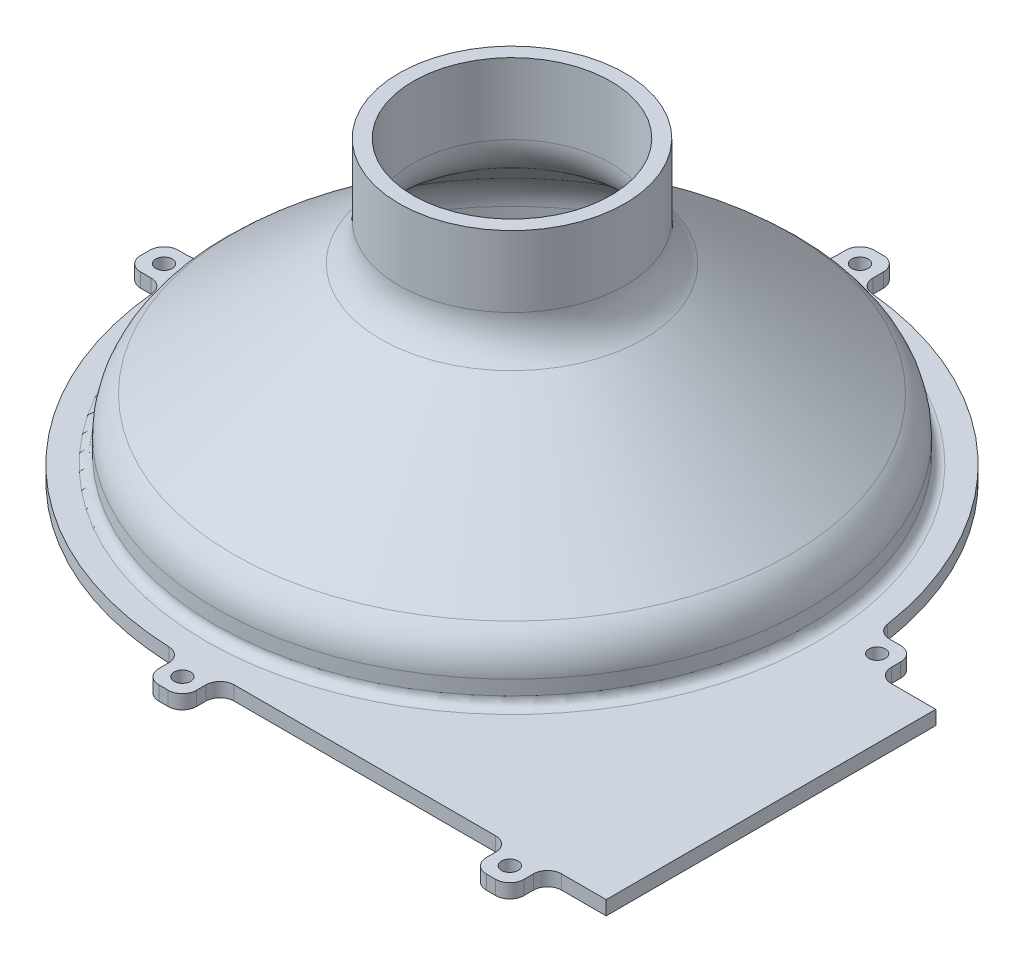
SolidWorks part; units mm, degrees
ref_plane "Front Plane" through (0, 0, 0) normal (0, 0, 1) x (1, 0, 0)
ref_plane "Top Plane" through (0, 0, 0) normal (0, 1, 0) x (1, 0, 0)
ref_plane "Right Plane" through (0, 0, 0) normal (1, 0, 0) x (0, 0, -1)
sketch "Sketch2" plane through (0, 0, 0) normal (0, 1, 0) x (1, 0, 0)
  line L0 (70, 0) -> (70, -70) construction
  line L1 (0, -70) -> (90, -70)
  line L3 (70, 0) -> (90, 0)
  line L4 (90, -70) -> (90, 0)
  arc A0 (70, 0) -> (0, -70) centre (0, 0) ccw
  circle A1 centre (0, 0) radius 60
  dimension "D1" = 140
  dimension "D4" = 120
  dimension "D3" = 20
extrude "Boss-Extrude1" add sketch "Sketch2" along normal blind 3
sketch "Sketch3" plane through (0, 3, 0) normal (0, 1, 0) x (1, 0, 0)
  circle A2 centre (0, 0) radius 60 construction
  circle A3 centre (0, 0) radius 60
  circle A4 centre (0, 0) radius 63
  dimension "D1" = 3
extrude "Boss-Extrude2" add sketch "Sketch3" along normal blind 10
sketch "Sketch6" plane through (0, 0, 0) normal (1, 0, 0) x (0, 0, -1)
  line L0 (-63, 13) -> (-24, 43)
  line L1 (-24, 43) -> (-21, 43)
  line L2 (-21, 43) -> (-60, 13)
  line L3 (63, 13) -> (-63, 13) construction
  line L4 (-63, 13) -> (-60, 13)
  line L5 (0, 0) -> (0, 43) construction
  line L6 (-70, 0) -> (70, 0) construction
  line L7 (-21, 43) -> (0, 43) construction
  dimension "D1" = 3
  dimension "D2" = 30
  dimension "D3" = 24
revolve "Revolve1" add sketch "Sketch6" angle 360 about L5
sketch "Sketch7" plane through (0, 43, 0) normal (0, 1, 0) x (1, 0, 0)
  circle A0 centre (0, 0) radius 24
  circle A1 centre (0, 0) radius 21
  circle A2 centre (0, 0) radius 21 construction
  circle A3 centre (0, 0) radius 24 construction
extrude "Boss-Extrude3" add sketch "Sketch7" along normal blind 20
fillet "Fillet1" radius 10 4 edges at (0, 43, -21) (0, 13, -60) (0, 13, 63) (0, 43, 24)
fillet "Fillet2" radius 2 1 edges at (0, 3, 63)
sketch "Sketch8" plane through (0, 0, 0) normal (0, -1, 0) x (1, 0, 0)
  line L21 (90, 0) -> (70, 0) construction
  line L22 (77.5414, 0) -> (69.5414, 0)
  line L23 (77.5414, 0) -> (77.5414, -8)
  line L24 (77.5414, -8) -> (69.5414, -8)
  line L25 (69.5414, 0) -> (69.5414, -8)
  line L26 (73.5414, 0) -> (73.5414, -8) construction
  line L27 (0, 70) -> (90, 70) construction
  line L28 (77.5414, 70) -> (69.5414, 70)
  line L29 (77.5414, 70) -> (77.5414, 78)
  line L30 (77.5414, 78) -> (69.5414, 78)
  line L31 (69.5414, 70) -> (69.5414, 78)
  line L32 (73.5414, 78) -> (73.5414, 70) construction
  line L33 (-73.8856, 4) -> (-73.8856, -4) construction
  line L34 (-69.8856, 4) -> (-77.8856, 4)
  line L35 (-69.8856, 4) -> (-69.8856, -4)
  line L36 (-69.8856, -4) -> (-77.8856, -4)
  line L37 (-77.8856, 4) -> (-77.8856, -4)
  line L38 (0, -69.8856) -> (0, -77.8856) construction
  line L39 (-4, -69.8856) -> (4, -69.8856)
  line L40 (-4, -69.8856) -> (-4, -77.8856)
  line L41 (-4, -77.8856) -> (4, -77.8856)
  line L42 (4, -69.8856) -> (4, -77.8856)
  line L43 (4, 78) -> (4, 70) construction
  line L44 (0, 70) -> (8, 70)
  line L45 (0, 70) -> (0, 78)
  line L46 (0, 78) -> (8, 78)
  line L47 (8, 70) -> (8, 78)
  arc A23 (0, 70) -> (70, 0) centre (0, 0) ccw construction
  circle A24 centre (73.5414, -4) radius 1.75
  circle A25 centre (73.5414, 74) radius 1.75
  circle A26 centre (-73.8856, 0) radius 1.75
  circle A27 centre (0, -73.8856) radius 1.75
  circle A28 centre (4, 74) radius 1.75
  dimension "D3" = 3.5
  dimension "D5" = 3.5
  dimension "D8" = 3.5
  dimension "D11" = 3.5
  dimension "D13" = 3.5
  dimension "D1" = 8
  dimension "D2" = 8
  dimension "D4" = 8
  dimension "D6" = 8
  dimension "D7" = 8
  dimension "D9" = 8
  dimension "D10" = 8
  dimension "D12" = 8
extrude "Boss-Extrude4" add sketch "Sketch8" against normal up to surface (3 mm away) up to face at (0, 3, 65)
fillet "Fillet3" radius 3 19 edges at (77.5414, 1.5, 0) (69.5414, 1.5, -8) (77.5414, 1.5, -8) (77.5414, 1.5, 70) (77.5414, 1.5, 78) (69.5414, 1.5, 78) (69.5414, 1.5, 70) (8, 1.5, 70) (8, 1.5, 78) (0, 1.5, 78) (0, 1.5, 70) (-69.8856, 1.5, 4) (-77.8856, 1.5, 4) (-77.8856, 1.5, -4) (-69.8856, 1.5, -4) (-4, 1.5, -77.8856) (4, 1.5, -77.8856) (4, 1.5, -69.8856) (-4, 1.5, -69.8856)
equation "\"LoftHeight\"= 30"
